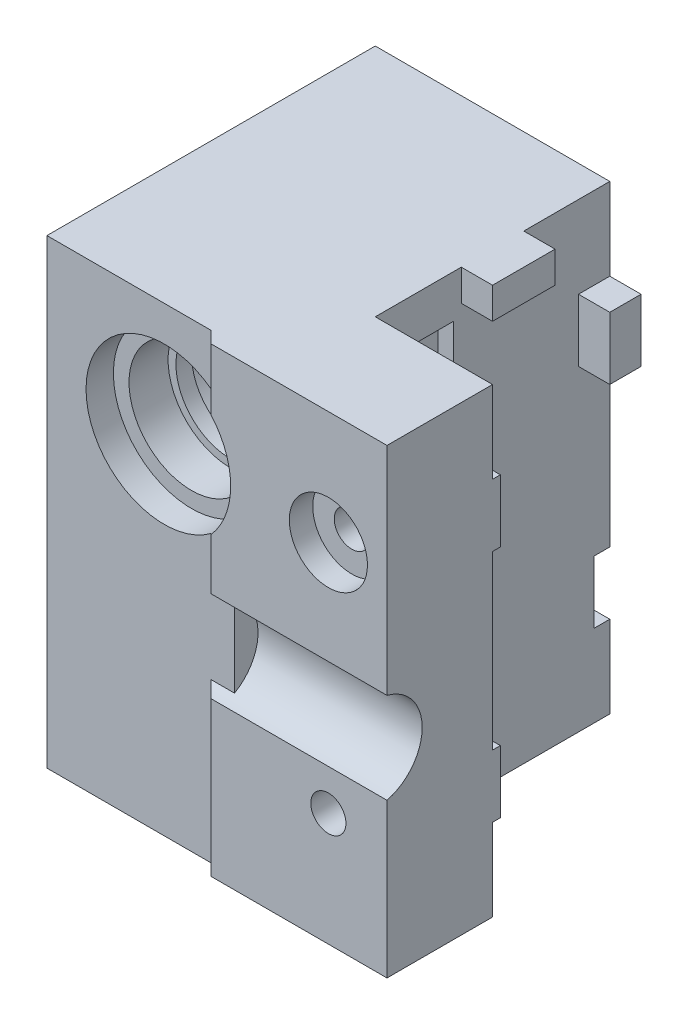
SolidWorks part; units mm, degrees
material "3D printed plastic"
ref_plane "Front Plane" through (0, 0, 0) normal (0, 0, 1) x (1, 0, 0)
ref_plane "Top Plane" through (0, 0, 0) normal (0, 1, 0) x (1, 0, 0)
ref_plane "Right Plane" through (0, 0, 0) normal (1, 0, 0) x (0, 0, -1)
sketch "Sketch1" plane through (0, 0, 0) normal (0, 0, 1) x (1, 0, 0)
  line L0 (0, 0) -> (0, -44.5) construction
  line L1 (-15, 14.5) -> (15, 14.5)
  line L2 (-15, 14.5) -> (-15, -44.5)
  line L3 (-15, -44.5) -> (15, -44.5)
  line L4 (15, 14.5) -> (15, -44.5)
  circle A0 centre (0, 0) radius 7
  dimension "D1" = 30
  dimension "D4" = 14
  dimension "D2" = 14.5
  dimension "D3" = 59
extrude "Boss-Extrude1" add sketch "Sketch1" against normal blind 30
sketch "Sketch2" plane through (0, -44.5, 0) normal (0, -1, 0) x (1, 0, 0)
  line L0 (-15, -30) -> (-15, 0) construction
  line L2 (-15, -30) -> (15, -30) construction
  line L5 (15, -30) -> (15, 0) construction
  line L6 (-15, -30) -> (15, -30)
  line L7 (-15, -30) -> (-15, -28)
  line L8 (-15, -28) -> (15, -28)
  line L9 (15, -30) -> (15, -28)
  dimension "D1" = 2
extrude "Cut-Extrude1" cut sketch "Sketch2" against normal mid plane 8 from offset 14.5 offset against normal yes
sketch "Sketch4" plane through (0, 0, 0) normal (0, 0, 1) x (1, 0, 0)
  line L0 (-15, -44.5) -> (15, -44.5) construction
  line L1 (-15, 14.5) -> (30, 14.5)
  line L2 (-15, 14.5) -> (-15, -44.5)
  line L3 (-15, -44.5) -> (30, -44.5)
  line L4 (30, 14.5) -> (30, -44.5)
  line L5 (15, -44.5) -> (15, 14.5) construction
  circle A0 centre (0, 0) radius 7
  circle A2 centre (0, 0) radius 7 construction
  dimension "D1" = 15
extrude "Boss-Extrude2" add sketch "Sketch4" along normal blind 12
sketch "Sketch5" plane through (0, 0, 12) normal (0, 0, 1) x (1, 0, 0)
  circle A0 centre (0, 0) radius 8
  dimension "D1" = 16
extrude "Cut-Extrude3" cut sketch "Sketch5" against normal blind 8.5
sketch "Sketch8" plane through (0, 0, 12) normal (0, 0, 1) x (1, 0, 0)
  circle A0 centre (0, 0) radius 10
  dimension "D1" = 20
extrude "Cut-Extrude5" cut sketch "Sketch8" against normal blind 3.5
sketch "Sketch11" plane through (0, 0, 12) normal (0, 0, 1) x (1, 0, 0)
  line L0 (-15, -44.5) -> (30, -44.5) construction
  line L1 (30, 14.5) -> (8, 14.5)
  line L2 (30, 14.5) -> (30, -44.5)
  line L3 (30, -44.5) -> (8, -44.5)
  line L4 (8, 14.5) -> (8, 6)
  line L9 (8, -6) -> (8, -44.5)
  arc A0 (8, -6) -> (8, 6) centre (0, 0) ccw
  circle A1 centre (0, 0) radius 10 construction
  dimension "D1" = 22
extrude "Boss-Extrude4" add sketch "Sketch11" along normal blind 1.5
sketch "Sketch12" plane through (30, 0, 0) normal (1, 0, 0) x (0, 0, -1)
  line L0 (-13.5, -44.5) -> (-13.5, 14.5) construction
  line L1 (0, -19) -> (-15, -19) construction
  line L3 (0, -44.5) -> (0, 14.5) construction
  line L4 (30, -44.5) -> (0, -44.5) construction
  circle A0 centre (-15, -19) radius 6
  dimension "D1" = 12
  dimension "D2" = 1.5
  dimension "D3" = 25.5
extrude "Cut-Extrude7" cut sketch "Sketch12" against normal up to surface (22 mm away) up to face at (8, -20.4375, 13.125)
chamfer "Chamfer1" distance 2 angle 45 3 edges
other "Move Face1" face at (8, -19, 10.5) offset 1 parameters "D1"=1
sketch "Sketch16" plane through (30, 0, 0) normal (1, 0, 0) x (0, 0, -1)
  line L0 (0, -44.5) -> (0, 14.5) construction
  line L1 (0, 4) -> (1, 4)
  line L2 (0, 4) -> (0, -4)
  line L3 (0, -4) -> (1, -4)
  line L4 (1, 4) -> (1, -4)
  line L5 (1, 0) -> (1, -30) construction
  line L6 (0, -26) -> (1, -26)
  line L7 (0, -26) -> (0, -34)
  line L8 (0, -34) -> (1, -34)
  line L9 (1, -26) -> (1, -34)
  line L10 (1, -15) -> (0, -15) construction
  dimension "D1" = 8
  dimension "D2" = 1
  dimension "D3" = 30
extrude "Boss-Extrude5" add sketch "Sketch16" against normal up to surface (15 mm away) up to face at (15, -26.1875, -25.75)
sketch "Sketch14" plane through (0, 0, 13.5) normal (0, 0, 1) x (1, 0, 0)
  line L0 (22.5, -30) -> (22.5, 0) construction
  line L1 (22.5, -15) -> (-15, -15) construction
  line L2 (-15, 14.5) -> (-15, -44.5) construction
  line L4 (30, -13.1905) -> (30, 14.5) construction
  circle A0 centre (22.5, 0) radius 2.25
  circle A1 centre (22.5, -30) radius 2.25
  dimension "D1" = 30
  dimension "D3" = 4.5
  dimension "D2" = 7.5
extrude "Cut-Extrude9" cut sketch "Sketch14" against normal through all
sketch "Sketch17" plane through (30, 0, 0) normal (1, 0, 0) x (0, 0, -1)
  line L0 (-16.5, -13.1905) -> (-16.5, -9.5)
  line L2 (-30.5, -9.5) -> (-30.5, -44.5)
  line L3 (-30.5, -44.5) -> (-13.5, -44.5)
  line L4 (-16.5, -40.5) -> (-16.5, -24.8095)
  line L5 (-15, -19) -> (-15, -10.6102) construction
  line L6 (-13.5, -13.1905) -> (-13.5, 14.5) construction
  line L8 (-13.5, -44.5) -> (0, -44.5) construction
  line L9 (-13.5, -44.5) -> (-13.5, -40.5)
  line L10 (-13.5, -44.5) -> (-13.5, -24.8095) construction
  line L12 (-16.5, -9.5) -> (-30.5, -9.5)
  line L13 (-13.5, -40.5) -> (-16.5, -40.5)
  arc A0 (-16.5, -13.1905) -> (-16.5, -24.8095) centre (-15, -19) ccw
  dimension "D1" = 14
  dimension "D2" = 4
  dimension "D3" = 35
extrude "Boss-Extrude6" add sketch "Sketch17" against normal blind 20 separate body
sketch "Sketch18" plane through (0, 0, 13.5) normal (0, 0, 1) x (1, 0, 0)
  circle A0 centre (22.5, 0) radius 5
  dimension "D1" = 10
extrude "Cut-Extrude10" cut sketch "Sketch18" against normal blind 3
sketch "Sketch19" plane through (0, 0, 30.5) normal (0, 0, 1) x (1, 0, 0)
  circle A0 centre (22.5, -30) radius 2.25
  circle A1 centre (22.5, -30) radius 2.25 construction
extrude "Cut-Extrude11" cut sketch "Sketch19" against normal through all
sketch "Sketch20" plane through (0, 0, 30.5) normal (0, 0, 1) x (1, 0, 0)
  circle A0 centre (22.5, -30) radius 5
  circle A2 centre (22.5, 0) radius 5 construction
extrude "Cut-Extrude12" cut sketch "Sketch20" against normal blind 7
chamfer "Chamfer2" distance 8 angle 45 1 edges at (20, -9.5, 30.5)
sketch "Sketch21" plane through (15, 0, 0) normal (1, 0, 0) x (0, 0, -1)
  line L0 (0, 4) -> (0, 14.5) construction
  line L1 (0, 9) -> (10, 9)
  line L2 (0, 9) -> (0, 4)
  line L3 (0, -9) -> (10, -9)
  line L4 (10, 9) -> (10, -9)
  line L5 (0, -26) -> (0, -4) construction
  line L6 (0, -21) -> (10, -21)
  line L7 (0, -21) -> (0, -26)
  line L8 (0, -39) -> (10, -39)
  line L9 (10, -21) -> (10, -39)
  line L10 (0, -4) -> (0, -9)
  line L11 (1, -26) -> (0, -26)
  line L12 (1, -26) -> (1, -34)
  line L13 (1, -34) -> (0, -34)
  line L15 (1, 4) -> (0, 4)
  line L16 (1, 4) -> (1, -4)
  line L17 (1, -4) -> (0, -4)
  line L18 (0, -34) -> (0, -39)
  dimension "D1" = 18
  dimension "D2" = 10
extrude "Cut-Extrude13" cut sketch "Sketch21" against normal blind 2
sketch "Sketch22" plane through (0, 0, -28) normal (0, 0, -1) x (-1, 0, 0)
  line L0 (-0.0016, -30) -> (15, -30) construction
  line L1 (15, -26) -> (15, -34) construction
  circle A0 centre (-0.0016, -30) radius 3.3
  dimension "D1" = 6.6
  dimension "D2" = 15.0016
extrude "Cut-Extrude14" cut sketch "Sketch22" against normal blind 15
sketch "Sketch23" plane through (0, 0, -28) normal (0, 0, -1) x (-1, 0, 0)
  line L0 (-5.1016, -32.9445) -> (-5.1016, -44.5)
  line L1 (-0.0016, -35.889) -> (5.0984, -32.9445) construction
  line L2 (5.0984, -32.9445) -> (5.0984, -27.0555)
  line L3 (5.0984, -27.0555) -> (-0.0016, -24.111)
  line L4 (-0.0016, -24.111) -> (-5.1016, -27.0555)
  line L5 (-5.1016, -27.0555) -> (-5.1016, -32.9445)
  line L6 (-5.1016, -32.9445) -> (-0.0016, -35.889) construction
  line L7 (15, -44.5) -> (-15, -44.5) construction
  line L8 (-5.1016, -44.5) -> (5.0984, -44.5)
  line L9 (5.0984, -44.5) -> (5.0984, -32.9445)
  circle A0 centre (-0.0016, -30) radius 5.1 construction
  dimension "D1" = 10.2
extrude "Cut-Extrude15" cut sketch "Sketch23" against normal blind 7 from offset 3 offset against normal yes
sketch "Sketch24" plane through (15, 0, 0) normal (1, 0, 0) x (0, 0, -1)
  line L0 (30, 14.5) -> (0, 14.5) construction
  line L1 (11, 14.5) -> (19, 14.5)
  line L2 (11, 14.5) -> (11, 10.5)
  line L3 (11, 10.5) -> (19, 10.5)
  line L4 (19, 14.5) -> (19, 10.5)
  line L5 (30, -26) -> (30, 14.5) construction
  line L6 (30, 4) -> (26, 4)
  line L7 (30, 4) -> (30, -4)
  line L8 (30, -4) -> (26, -4)
  line L9 (26, 4) -> (26, -4)
  line L10 (30, 0) -> (26, 0) construction
  line L11 (15, 14.5) -> (15, 10.5) construction
  line L12 (0, 9) -> (0, 14.5) construction
  dimension "D1" = 8
  dimension "D2" = 4
  dimension "D3" = 15
  dimension "D4" = 14.5
extrude "Boss-Extrude7" add sketch "Sketch24" along normal blind 4
sketch "Sketch25" plane through (0, 0, -30) normal (0, 0, -1) x (-1, 0, 0)
  line L0 (-8.1915, 5.7358) -> (-12.2077, 0)
  line L1 (-12.2077, 0) -> (-8.1915, -5.7358)
  line L2 (-12.2077, 0) -> (0, 0) construction
  arc A0 (-8.1915, -5.7358) -> (-8.1915, 5.7358) centre (0, 0) ccw
  dimension "D1" = 20
  dimension "D2" = 110
extrude "Cut-Extrude16" cut sketch "Sketch25" against normal offset from surface (31.5 mm away) 2 up to face at (8, 0, 3.5)
delete or keep bodies "Body-Delete1" type delete bodies bodies 120
